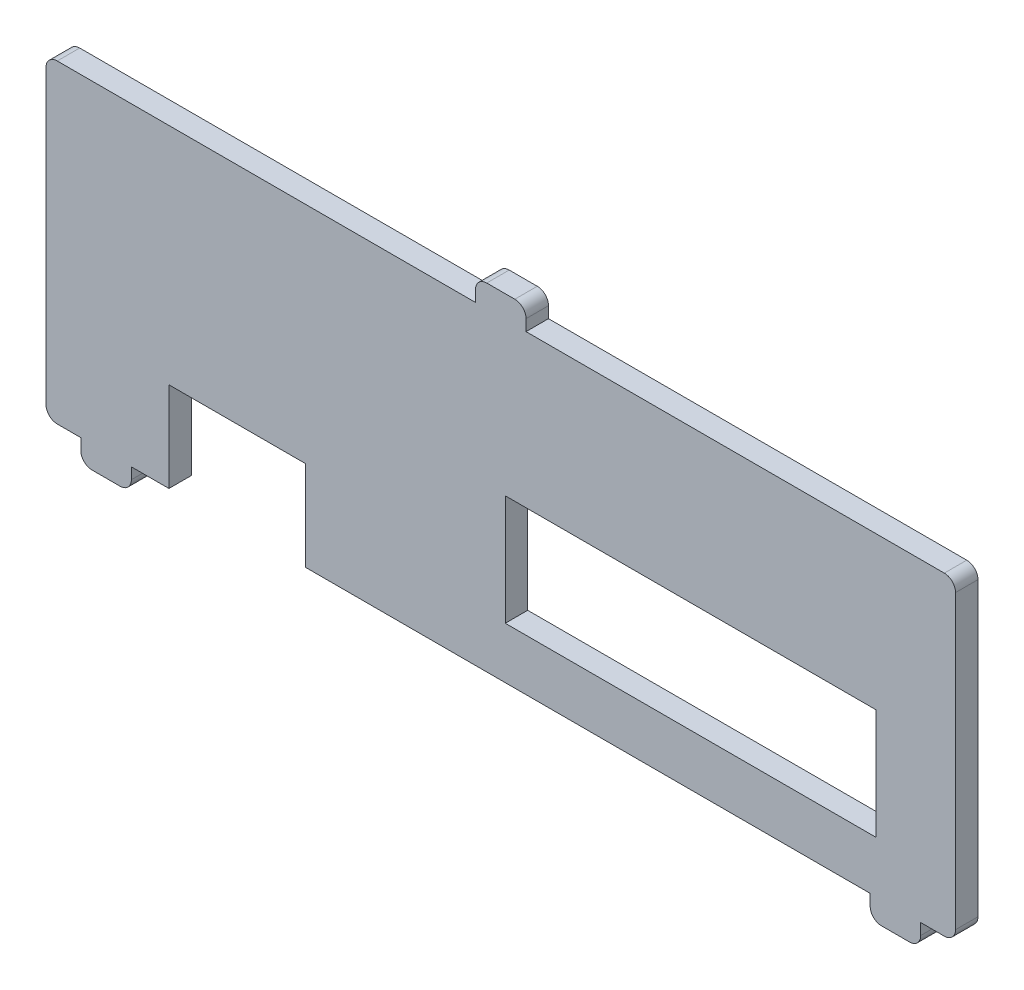
SolidWorks part; units mm, degrees
ref_plane "前基準面" through (0, 0, 0) normal (0, 0, 1) x (1, 0, 0)
ref_plane "上基準面" through (0, 0, 0) normal (0, 1, 0) x (1, 0, 0)
ref_plane "右基準面" through (0, 0, 0) normal (1, 0, 0) x (0, 0, -1)
sketch "Sketch1" plane through (0, 0, 0) normal (0, 0, 1) x (1, 0, 0)
  line L0 (0, 0) -> (0, 14) construction
  line L1 (-40.5, 14) -> (40.5, 14)
  line L2 (-40.5, 14) -> (-40.5, -14)
  line L3 (-40.5, -14) -> (40.5, -14)
  line L4 (40.5, 14) -> (40.5, -14)
  line L5 (-40.5, 14) -> (40.5, -14) construction
  line L6 (-40.5, -14) -> (40.5, 14) construction
  line L7 (0, 14) -> (0, -14) construction
  line L8 (-37.4, -14) -> (-32.9, -16) construction
  line L9 (-37.4, -14) -> (-32.9, -14)
  line L10 (-37.4, -14) -> (-37.4, -16)
  line L11 (-37.4, -16) -> (-32.9, -16)
  line L12 (-32.9, -14) -> (-32.9, -16)
  line L14 (37.4, -16) -> (32.9, -16)
  line L15 (32.9, -14) -> (32.9, -16)
  line L16 (37.4, -14) -> (32.9, -14)
  line L17 (37.4, -14) -> (37.4, -16)
  line L18 (0, 0) -> (0, 22.3502) construction
  line L19 (-2.25, 16) -> (2.25, 14) construction
  line L20 (-2.25, 14) -> (2.25, 14)
  line L21 (-2.25, 14) -> (-2.25, 16)
  line L22 (-2.25, 16) -> (2.25, 16)
  line L23 (2.25, 14) -> (2.25, 16)
  line L24 (2.25, 16) -> (-2.25, 14) construction
  line L25 (-37.4, -16) -> (-32.9, -14) construction
  point P0 (0, 0)
  point P14 (-35.15, -15)
  point P24 (0, 15)
  dimension "D1" = 81
  dimension "D2" = 28
  dimension "D3" = 2
  dimension "D4" = 4.5
  dimension "D5" = 35.15
  dimension "D6" = 2
  dimension "D7" = 4.5
extrude "Boss-Extrude1" add sketch "Sketch1" along normal mid plane 2 contours L4 L1 L2 L3 | L12 L3 L10 L11 | L17 L3 L15 L14 | L23 L22 L21 L20 region at (0, 0, 0) region at (-35.15, -15, 0) region at (35.15, -15, 0)
fillet "Fillet1" radius 1 10 edges at (-40.5, 14, 0) (-32.9, -16, 0) (-37.4, -16, 0) (-40.5, -14, 0) (32.9, -16, 0) (37.4, -16, 0) (40.5, -14, 0) (40.5, 14, 0) (2.25, 16, 0) (-2.25, 16, 0)
sketch "Sketch3" plane through (0, 0, -1) normal (0, 0, -1) x (-1, 0, 0)
  line L1 (-33.4, 0.4174) -> (-0.4, 0.4174)
  line L2 (-33.4, 0.4174) -> (-33.4, -9.4174)
  line L3 (-33.4, -9.4174) -> (-0.4, -9.4174)
  line L4 (-0.4, 0.4174) -> (-0.4, -9.4174)
  line L5 (-33.4, 0.4174) -> (-0.4, -9.4174) construction
  line L6 (-33.4, -9.4174) -> (-0.4, 0.4174) construction
  line L7 (-45.95, -16) -> (46.05, -16) construction
  line L8 (32.9, -14) -> (-32.9, -14) construction
  line L9 (17.4097, -6) -> (29.553, -6)
  line L10 (17.4097, -6) -> (17.4097, -14)
  line L11 (17.4097, -14) -> (29.553, -14)
  line L12 (29.553, -6) -> (29.553, -14)
  line L13 (17.4097, -6) -> (29.553, -14) construction
  line L14 (17.4097, -14) -> (29.553, -6) construction
  line L15 (45.05, 13) -> (45.05, -13) construction
  line L16 (-40.4, 13) -> (-40.4, -13) construction
  point P0 (-16.9, -4.5)
  point P11 (23.4813, -10)
  dimension "D1" = 23.5
  dimension "D2" = 11.5
  dimension "D3" = 9.8348
  dimension "D4" = 33
  dimension "D5" = 21.5687
  dimension "D6" = 6
extrude "Cut-Extrude1" cut sketch "Sketch3" against normal up to next
